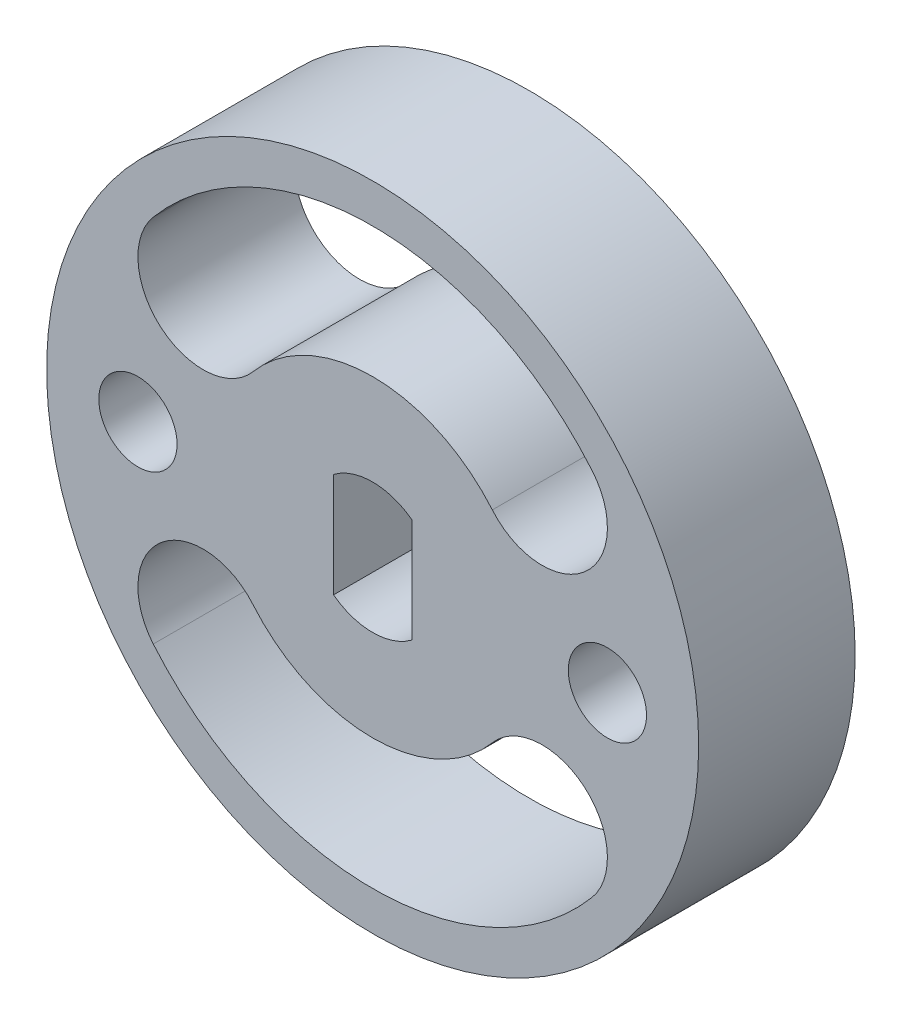
SolidWorks part; units mm, degrees
ref_plane "Front Plane" through (0, 0, 0) normal (0, 0, 1) x (1, 0, 0)
ref_plane "Top Plane" through (0, 0, 0) normal (0, 1, 0) x (1, 0, 0)
ref_plane "Right Plane" through (0, 0, 0) normal (1, 0, 0) x (0, 0, -1)
sketch "Sketch1" plane through (0, 0, 0) normal (0, 0, 1) x (1, 0, 0)
  line L0 (1500, 2000) -> (1500, 0)
  line L1 (1500, 0) -> (7500, 0)
  line L2 (10500, 0) -> (12500, 0)
  line L3 (0, 12500) -> (0, 2500)
  arc A0 (0, 2500) -> (1500, 2000) centre (0, 0) cw
  arc A1 (7500, 0) -> (10500, 0) centre (9000, 0) cw
  arc A2 (12500, 0) -> (0, 12500) centre (0, 0) ccw
  point P11 (0, 0)
  dimension "D1" = 1500
  dimension "D2" = 2500
  dimension "D4" = 12500
  dimension "D5" = 1500
  dimension "D3" = 9000
  dimension "D6" = 12500
extrude "Boss-Extrude1" add sketch "Sketch1" along normal blind 6000
mirror "Mirror4" about plane through (0, 12500, 6000) normal (1, 0, 0) of bodies 101
sketch "Sketch2" plane through (0, 0, 6000) normal (0, 0, 1) x (1, 0, 0)
  line L0 (-6500, 5477.2256) -> (6500, 5477.2256) construction
  arc A0 (-6500, 5477.2256) -> (6500, 5477.2256) centre (0, 0) cw construction
  arc A1 (8411.7647, 7088.1743) -> (-8411.7647, 7088.1743) centre (0, 0) ccw
  arc A2 (4588.2353, 3866.2769) -> (-4588.2353, 3866.2769) centre (0, 0) ccw
  arc A3 (4588.2353, 3866.2769) -> (8411.7647, 7088.1743) centre (6500, 5477.2256) ccw
  arc A4 (-8411.7647, 7088.1743) -> (-4588.2353, 3866.2769) centre (-6500, 5477.2256) ccw
  point P5 (0, 8500)
  point P13 (0, 6000)
  dimension "D2" = 13000
  dimension "D1" = 8500
  dimension "D3" = 6000
extrude "Cut-Extrude1" cut sketch "Sketch2" against normal through all
mirror "Mirror5" about plane through (-1500, 0, 6000) normal (0, 1, 0) of bodies 106
